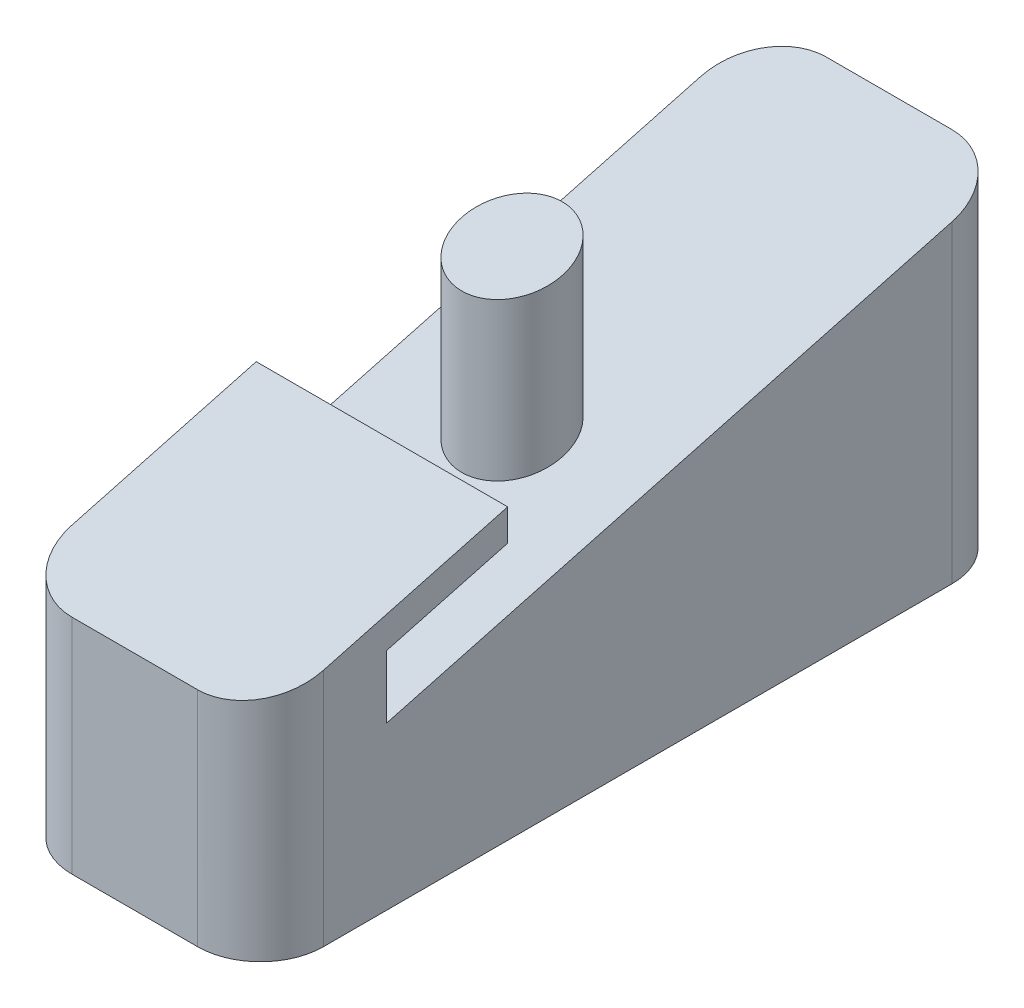
SolidWorks part; units mm, degrees
material "ABS"
ref_plane "Front Plane" through (0, 0, 0) normal (0, 0, 1) x (1, 0, 0)
ref_plane "Top Plane" through (0, 0, 0) normal (0, 1, 0) x (1, 0, 0)
ref_plane "Right Plane" through (0, 0, 0) normal (1, 0, 0) x (0, 0, -1)
sketch "Sketch1" plane through (0, 0, 0) normal (0, 1, 0) x (1, 0, 0)
  line L0 (-12.7, -25.4) -> (12.7, -25.4)
  line L1 (-12.7, -38.1) -> (12.7, -38.1)
  line L2 (-12.7, -38.1) -> (-12.7, 38.1)
  line L3 (-12.7, 38.1) -> (12.7, 38.1)
  line L4 (12.7, -38.1) -> (12.7, 38.1)
  line L5 (-12.7, -38.1) -> (12.7, 38.1) construction
  line L6 (-12.7, 38.1) -> (12.7, -38.1) construction
  point P0 (0, 0)
  dimension "D3" = 12.7
  dimension "D1" = 25.4
  dimension "D2" = 76.2
extrude "Boss-Extrude1" add sketch "Sketch1" along normal blind 33.3756 contours L1 L4 L0 L2 | L0 L4 L3 L2 region at (0, 0, -6.35) region at (0, 0, 31.75)
sketch "Sketch4" plane through (12.7, 0, 0) normal (1, 0, 0) x (0, 0, -1)
  line L0 (38.1, 33.3756) -> (-38.1, 33.3756)
  line L1 (-38.1, 33.3756) -> (-38.1, 12.9579)
  line L3 (-38.1, 12.9579) -> (38.1, 33.3756)
  line L4 (-38.1, 12.9579) -> (38.0791, 12.9579) construction
  line L6 (-38.1, 33.3756) -> (-38.1, 0) construction
  dimension "D1" = 15
extrude "Cut-Extrude2" cut sketch "Sketch4" against normal through all both and the other way through all
sketch "Sketch5" plane through (0, 21.6149, 5.7917) normal (0, 0.9659, 0.2588) x (1, 0, 0)
  line L0 (0, 45.44) -> (0, -33.448) construction
  line L1 (12.7, 45.44) -> (-12.7, 45.44) construction
  line L2 (-12.7, -33.448) -> (12.7, -33.448) construction
  line L3 (-12.7, 5.996) -> (12.7, 5.996) construction
  line L4 (-12.7, -33.448) -> (-12.7, 45.44) construction
  line L5 (12.7, 45.44) -> (12.7, -33.448) construction
  circle A0 centre (0, 5.996) radius 3.175
  dimension "D1" = 6.35
extrude "Cut-Extrude3" [suppressed] cut sketch "Sketch5" against normal blind 6.35
ref_point "Point1" [suppressed]
extrude "Boss-Extrude2" add sketch "Sketch1<5>" along normal blind 9.525 from surface contours L1 L4 L0 L2 region at (0, 0, 31.75) starting at face at (-3.175, 25.719, -9.525)
sketch "Sketch1<5>" plane through (0, 0, 0) normal (0, 1, 0) x (1, 0, 0) same geometry as "Sketch1"
sketch "Sketch7" plane through (0, 0, 25.4) normal (0, 0, -1) x (-1, 0, 0)
  line L1 (-12.7, 25.8858) -> (12.7, 25.8858)
  line L2 (-12.7, 25.8858) -> (-12.7, 22.7108)
  line L3 (-12.7, 22.7108) -> (12.7, 22.7108)
  line L4 (12.7, 25.8858) -> (12.7, 22.7108)
  line L5 (12.7, 25.8858) -> (12.7, 16.3608) construction
  dimension "D1" = 3.175
extrude "Boss-Extrude3" add sketch "Sketch7" along direction (0, 0.2588, -0.9659) on the side of the normal blind 12.7
fillet "Fillet1" radius 6.35 4 edges at (-12.7, 16.6878, -38.1) (-12.7, 11.2414, 38.1) (12.7, 11.2414, 38.1)
sketch "Sketch8" plane through (0, 0, 0) normal (0, -1, 0) x (1, 0, 0)
  circle A0 centre (0, 0) radius 5.08
  circle A1 centre (0, 0) radius 5.715
  dimension "D1" = 10.16
  dimension "D2" = 11.43
extrude "Boss-Extrude4" add sketch "Sketch8" against normal blind 15.875 from surface contours A0 region at (0, 0, 0) starting at face at (-1.0583, 28.5304, -20.0175)
extrude "Cut-Extrude4" cut sketch "Sketch8<3>" against normal blind 15.875 contours A0 | A1 A0 region at (0, 0, 0) region at (-5.5534, 0, 0)
sketch "Sketch8<3>" plane through (0, 0, 0) normal (0, -1, 0) x (1, 0, 0) same geometry as "Sketch8"
ref_point "Point2"
